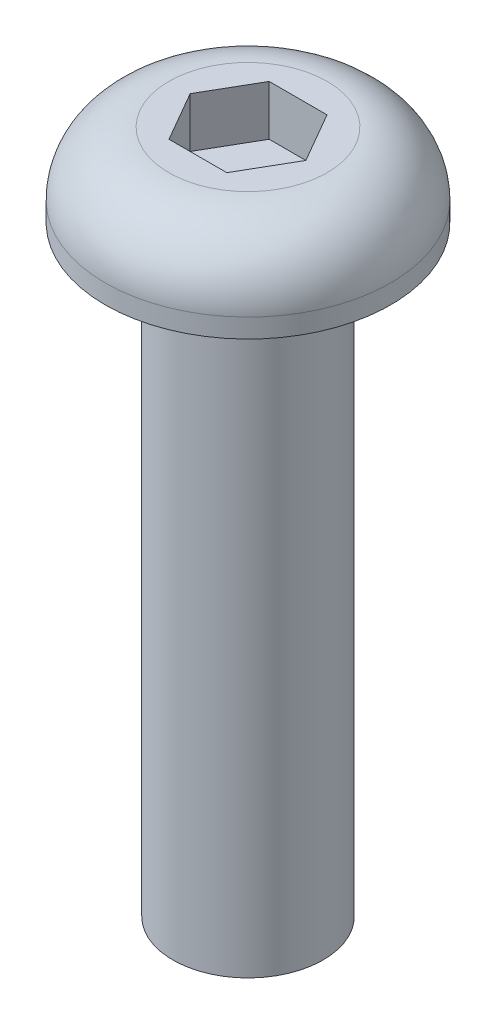
SolidWorks part; units mm, degrees
material "AISI 304"
ref_plane "Front Plane" through (0, 0, 0) normal (0, 0, 1) x (1, 0, 0)
ref_plane "Top Plane" through (0, 0, 0) normal (0, 1, 0) x (1, 0, 0)
ref_plane "Right Plane" through (0, 0, 0) normal (1, 0, 0) x (0, 0, -1)
sketch "Sketch1" plane through (0, 0, 0) normal (0, 0, 1) x (1, 0, 0)
  line L0 (1.5, 0) -> (2.85, 0)
  line L1 (2.85, 0) -> (2.85, 0.38)
  line L2 (1.58, 1.65) -> (0, 1.65)
  line L3 (1.5, 0) -> (1.5, -12)
  line L4 (1.5, -12) -> (0, -12)
  line L5 (0, -12) -> (0, 1.65)
  arc A0 (2.85, 0.38) -> (1.58, 1.65) centre (1.58, 0.38) ccw
  dimension "D1" = 1.5
  dimension "D2" = 12
  dimension "D3" = 2.85
  dimension "D4" = 1.65
  dimension "D5" = 0.38
revolve "Revolve1" add sketch "Sketch1" angle 360 about L5
sketch "Sketch2" plane through (0, 1.65, 0) normal (0, 1, 0) x (1, 0, 0)
  line L1 (0.5774, 1) -> (-0.5774, 1)
  line L2 (-0.5774, 1) -> (-1.1547, 0)
  line L3 (-1.1547, 0) -> (-0.5774, -1)
  line L4 (-0.5774, -1) -> (0.5774, -1)
  line L5 (0.5774, -1) -> (1.1547, 0)
  line L6 (1.1547, 0) -> (0.5774, 1)
  circle A0 centre (0, 0) radius 1 construction
  dimension "D1" = 2
extrude "Cut-Extrude1" cut sketch "Sketch2" against normal blind 1
